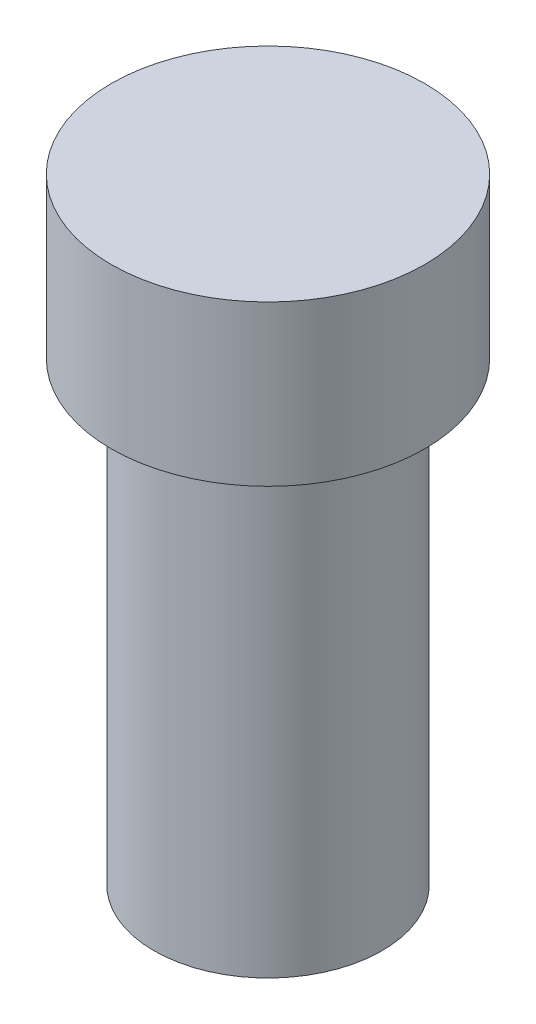
SolidWorks part; units mm, degrees
ref_plane "Front Plane" through (0, 0, 0) normal (0, 0, 1) x (1, 0, 0)
ref_plane "Top Plane" through (0, 0, 0) normal (0, 1, 0) x (1, 0, 0)
ref_plane "Right Plane" through (0, 0, 0) normal (1, 0, 0) x (0, 0, -1)
sketch "Sketch1" plane through (0, 0, 0) normal (0, 1, 0) x (1, 0, 0)
  circle A0 centre (0, 0) radius 2.75
  circle A1 centre (0, 0) radius 2
  dimension "D1" = 5.5
  dimension "D2" = 4
extrude "Boss-Extrude1" add sketch "Sketch1" along normal blind 2.8 contours A0
extrude "Boss-Extrude2" add sketch "Sketch1<3>" against normal blind 8 contours A1
sketch "Sketch1<3>" plane through (0, 0, 0) normal (0, 1, 0) x (1, 0, 0) same geometry as "Sketch1"
